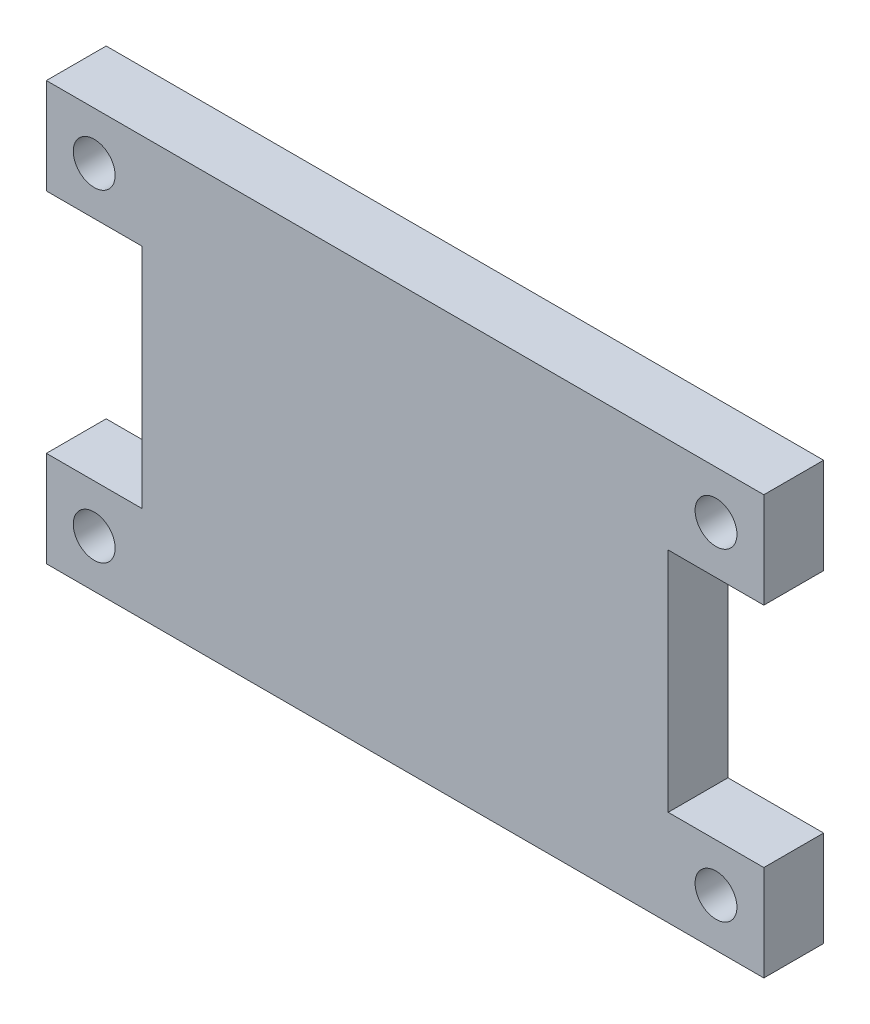
SolidWorks part; units mm, degrees
ref_plane "前基準面" through (0, 0, 0) normal (0, 0, 1) x (1, 0, 0)
ref_plane "上基準面" through (0, 0, 0) normal (0, 1, 0) x (1, 0, 0)
ref_plane "右基準面" through (0, 0, 0) normal (1, 0, 0) x (0, 0, -1)
sketch "草圖1" plane through (0, 0, 0) normal (0, 0, 1) x (1, 0, 0)
  line L1 (-22, 17.5) -> (22, 17.5)
  line L2 (-22, 17.5) -> (-22, -17.5)
  line L3 (-22, -17.5) -> (22, -17.5)
  line L4 (22, 17.5) -> (22, -17.5)
  line L5 (-22, 17.5) -> (22, -17.5) construction
  line L6 (-22, -17.5) -> (22, 17.5) construction
  line L7 (-30, 9.5) -> (-22, 9.5)
  line L8 (-30, 9.5) -> (-30, 17.5)
  line L9 (-30, 17.5) -> (-22, 17.5)
  line L10 (-22, 9.5) -> (-22, 17.5)
  line L11 (-30, 9.5) -> (-22, 17.5) construction
  line L12 (-30, 17.5) -> (-22, 9.5) construction
  line L13 (-30, -9.5) -> (-22, -9.5)
  line L14 (-30, -9.5) -> (-30, -17.5)
  line L15 (-30, -17.5) -> (-22, -17.5)
  line L16 (-22, -9.5) -> (-22, -17.5)
  line L17 (-30, -9.5) -> (-22, -17.5) construction
  line L18 (-30, -17.5) -> (-22, -9.5) construction
  line L19 (30, 9.5) -> (22, 9.5)
  line L20 (30, 9.5) -> (30, 17.5)
  line L21 (30, 17.5) -> (22, 17.5)
  line L22 (22, 9.5) -> (22, 17.5)
  line L23 (30, 9.5) -> (22, 17.5) construction
  line L24 (30, 17.5) -> (22, 9.5) construction
  line L25 (30, -9.5) -> (22, -9.5)
  line L26 (30, -9.5) -> (30, -17.5)
  line L27 (30, -17.5) -> (22, -17.5)
  line L28 (22, -9.5) -> (22, -17.5)
  line L29 (30, -9.5) -> (22, -17.5) construction
  line L30 (30, -17.5) -> (22, -9.5) construction
  circle A0 centre (-26, 13.5) radius 1.75
  circle A1 centre (26, 13.5) radius 1.75
  circle A2 centre (26, -13.5) radius 1.75
  circle A3 centre (-26, -13.5) radius 1.75
  point P0 (0, 0)
  point P6 (-26, 13.5)
  point P7 (-26, -13.5)
  point P11 (26, 13.5)
  point P15 (26, -13.5)
  dimension "D4" = 3.5
  dimension "D1" = 8
  dimension "D2" = 44
  dimension "D3" = 35
extrude "填料-伸長1" add sketch "草圖1" along normal blind 5 contours L9 L8 L7 L2 | L20 L21 L4 L19 | L27 L26 L25 L4 | L14 L15 L2 L13 | L4 L1 L2 L3 region at (0, 0, 0) region at (-22.1131, 13.5, 0) region at (26, 17.3869, 0) region at (-22.1131, -13.5, 0) region at (26, -9.6131, 0)
